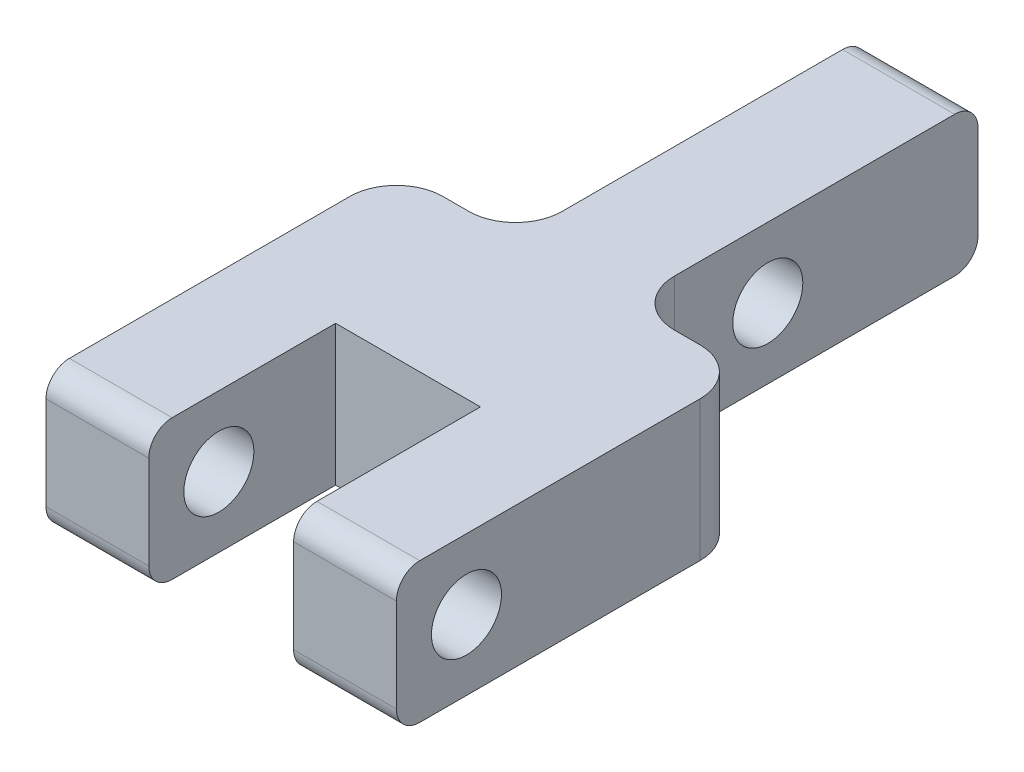
SolidWorks part; units mm, degrees
ref_plane "Alzado" through (0, 0, 0) normal (0, 0, 1) x (1, 0, 0)
ref_plane "Planta" through (0, 0, 0) normal (0, 1, 0) x (1, 0, 0)
ref_plane "Vista lateral" through (0, 0, 0) normal (1, 0, 0) x (0, 0, -1)
sketch "Croquis1" plane through (0, 0, 0) normal (1, 0, 0) x (0, 0, -1)
  line L0 (-14, 3) -> (14, 3)
  line L2 (-15, 0) -> (15, 0) construction
  line L3 (-15, 2) -> (-15, -2)
  line L4 (-14, -3) -> (14, -3)
  line L5 (15, 2) -> (15, -2)
  arc A0 (-15, -2) -> (-14, -3) centre (-14, -2) ccw
  arc A1 (-15, 2) -> (-14, 3) centre (-14, 2) cw
  arc A2 (14, -3) -> (15, -2) centre (14, -2) ccw
  arc A3 (14, 3) -> (15, 2) centre (14, 2) cw
  point P1 (0, 0)
  point P9 (-15, -3)
  point P13 (-15, 3)
  point P16 (15, -3)
  point P19 (15, 3)
  dimension "D3" = 1
  dimension "D4" = 1
  dimension "D1" = 3
  dimension "D2" = 30
extrude "Saliente-Extruir1" add sketch "Croquis1" along normal mid plane 4.8
sketch "Croquis2" plane through (0, 0, 0) normal (1, 0, 0) x (0, 0, -1)
  line L0 (-15, 2) -> (-15, -2) construction
  line L1 (15, -2) -> (15, 2) construction
  circle A0 centre (-12, 0) radius 1.5
  circle A1 centre (6, 0) radius 1.5
  dimension "D1" = 3
  dimension "D3" = 3
  dimension "D2" = 3
  dimension "D4" = 9
extrude "Cortar-Extruir1" cut sketch "Croquis2" against normal through all both and the other way through all
sketch "Croquis3" plane through (0, 0, 0) normal (1, 0, 0) x (0, 0, -1)
  line L0 (-15, 2) -> (-15, -2) construction
  line L1 (-15, 2) -> (-15, -2)
  line L2 (-14, 3) -> (0, 3)
  line L3 (14, 3) -> (-14, 3) construction
  line L4 (0, 3) -> (0, -3)
  line L5 (-14, -3) -> (14, -3) construction
  line L6 (0, -3) -> (-14, -3)
  circle A0 centre (-12, 0) radius 1.5 construction
  circle A1 centre (-12, 0) radius 1.5
  arc A2 (-14, 3) -> (-15, 2) centre (-14, 2) ccw construction
  arc A3 (-14, 3) -> (-15, 2) centre (-14, 2) ccw
  arc A4 (-15, -2) -> (-14, -3) centre (-14, -2) ccw construction
  arc A5 (-15, -2) -> (-14, -3) centre (-14, -2) ccw
extrude "Saliente-Extruir2" add sketch "Croquis3" along normal mid plane 15
sketch "Croquis4" plane through (0, 0, 0) normal (1, 0, 0) x (0, 0, -1)
  line L0 (-14, 3) -> (-7, 3)
  line L1 (0, 3) -> (-14, 3) construction
  line L2 (-7, 3) -> (-7, -3)
  line L3 (-14, -3) -> (0, -3) construction
  line L4 (-15, 2) -> (-15, -2)
  line L5 (-14, -3) -> (0, -3)
  line L6 (0, -3) -> (0, 3)
  line L7 (0, 3) -> (-14, 3)
  line L8 (-15, 2) -> (-15, -2)
  line L12 (-7, -3) -> (-14, -3)
  arc A2 (-14, 3) -> (-15, 2) centre (-14, 2) ccw
  arc A3 (-15, -2) -> (-14, -3) centre (-14, -2) ccw
  arc A4 (-14, 3) -> (-15, 2) centre (-14, 2) ccw
  arc A5 (-15, -2) -> (-14, -3) centre (-14, -2) ccw
  dimension "D2" = 8
  dimension "D1" = 0
extrude "Cortar-Extruir2" cut sketch "Croquis4" against normal mid plane 6.2
fillet "Redondeo1" radius 2 4 edges at (2.4, 0, 0) (-2.4, 0, 0) (7.5, 0, 0) (-7.5, 0, 0)
